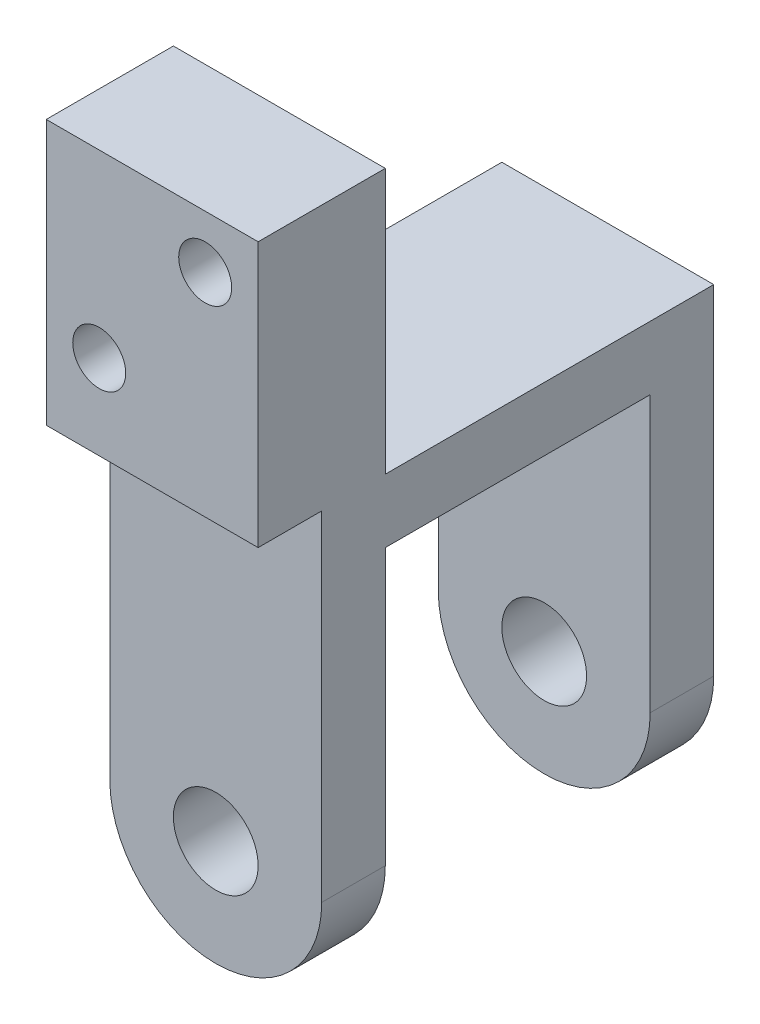
SolidWorks part; units mm, degrees
ref_plane "前视基准面" through (0, 0, 0) normal (0, 0, 1) x (1, 0, 0)
ref_plane "上视基准面" through (0, 0, 0) normal (0, 1, 0) x (1, 0, 0)
ref_plane "右视基准面" through (0, 0, 0) normal (1, 0, 0) x (0, 0, -1)
sketch "草图1" plane through (0, 0, 0) normal (0, 0, 1) x (1, 0, 0)
  line L1 (-26.3979, -19.9986) -> (-26.3979, 12.0014)
  line L2 (-26.3979, 12.0014) -> (-46.3979, 12.0014)
  line L3 (-46.3979, 12.0014) -> (-46.3979, -19.9986)
  arc A0 (-46.3979, -19.9986) -> (-26.3979, -19.9986) centre (-36.3979, -19.9986) ccw
  dimension "D1" = 20
  dimension "D2" = 32
extrude "凸台-拉伸1" add sketch "草图1" along normal blind 37 contours L3 A0 L1 L2
sketch "草图5" plane through (0, 0, 0) normal (0, 0, -1) x (-1, 0, 0)
  circle A0 centre (36.3979, -19.9986) radius 4
extrude "切除-拉伸1" cut sketch "草图5" against normal through all
sketch "草图6" plane through (-26.3979, 0, 0) normal (1, 0, 0) x (0, 0, -1)
  line L0 (-31, 6.0014) -> (-6, 6.0014)
  line L1 (-6, 6.0014) -> (-6, -33.8249)
  line L2 (-31, 6.0014) -> (-31, -33.8249)
  line L4 (-37, 12.0014) -> (0, 12.0014) construction
  line L5 (-37, -19.9986) -> (-37, 12.0014) construction
  line L6 (0, -19.9986) -> (0, 12.0014) construction
  line L7 (-31, -33.8249) -> (-6, -33.8249)
  dimension "D1" = 6
  dimension "D2" = 6
  dimension "D3" = 6
extrude "切除-拉伸2" cut sketch "草图6" against normal through all
sketch "草图8" plane through (0, 0, 37) normal (0, 0, 1) x (1, 0, 0)
  line L0 (-26.3979, 12.0014) -> (-26.3979, 37.0014)
  line L1 (-26.3979, 37.0014) -> (-46.3979, 37.0014)
  line L2 (-46.3979, 37.0014) -> (-46.3979, 12.0014)
  line L4 (-46.3979, 12.0014) -> (-26.3979, 12.0014)
  dimension "D1" = 25
extrude "凸台-拉伸5" add sketch "草图8" along normal blind 6 separate body contours L2 L4 L0 L1
extrude "凸台-拉伸6" add sketch "草图8<3>" along normal blind 6
sketch "草图8<3>" plane through (0, 0, 37) normal (0, 0, 1) x (1, 0, 0) same geometry as "草图8"
sketch "草图10" plane through (0, 0, 37) normal (0, 0, -1) x (-1, 0, 0)
  line L0 (26.3979, 12.0014) -> (46.3979, 12.0014)
  line L1 (46.3979, 12.0014) -> (46.3979, 37.0014)
  line L2 (46.3979, 37.0014) -> (26.3979, 37.0014)
  line L3 (26.3979, 37.0014) -> (26.3979, 12.0014)
extrude "凸台-拉伸7" add sketch "草图10" along normal blind 6
sketch "草图11" plane through (0, 0, 31) normal (0, 0, -1) x (-1, 0, 0)
  line L1 (26.3979, 37.0014) -> (26.3979, 12.0014) construction
  line L4 (46.3979, 37.0014) -> (26.3979, 37.0014) construction
  circle A0 centre (31.3979, 32.0014) radius 2.5
  circle A1 centre (41.3979, 20.0014) radius 2.5
  dimension "D1" = 5
  dimension "D2" = 5
  dimension "D3" = 10
  dimension "D4" = 5
  dimension "D5" = 5
  dimension "D6" = 12
extrude "切除-拉伸3" cut sketch "草图11" against normal through all
